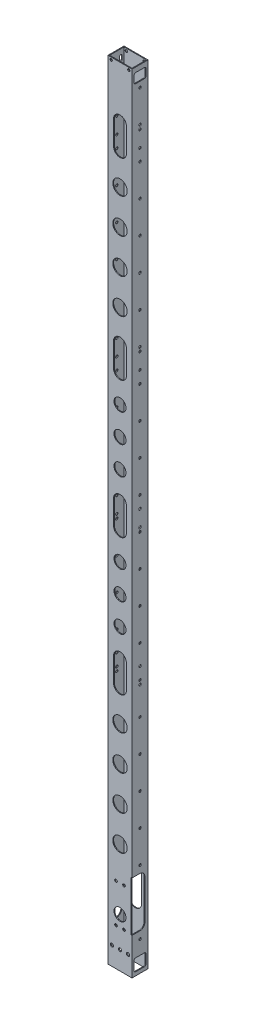
SolidWorks part; units mm, degrees
material "6061 合金"
ref_plane "Front" through (0, 0, 0) normal (0, 0, 1) x (1, 0, 0)
ref_plane "Top" through (0, 0, 0) normal (0, 1, 0) x (1, 0, 0)
ref_plane "Right" through (0, 0, 0) normal (1, 0, 0) x (0, 0, -1)
sketch "草图1" plane through (0, 0, 0) normal (0, 1, 0) x (1, 0, 0)
  line L1 (-15, -10) -> (15, -10)
  line L2 (-15, -10) -> (-15, 10)
  line L3 (-15, 10) -> (15, 10)
  line L4 (15, -10) -> (15, 10)
  line L5 (-15, -10) -> (15, 10) construction
  line L6 (-15, 10) -> (15, -10) construction
  line L7 (-14, -9) -> (14, -9)
  line L8 (-14, -9) -> (-14, 9)
  line L9 (-14, 9) -> (14, 9)
  line L10 (14, -9) -> (14, 9)
  line L11 (-14, -9) -> (14, 9) construction
  line L12 (-14, 9) -> (14, -9) construction
  point P0 (0, 0)
  point P5 (0, 0)
  dimension "D1" = 20
  dimension "D2" = 30
  dimension "D3" = 1
  dimension "D4" = 1
extrude "凸台-拉伸1" add sketch "草图1" along normal blind 980
sketch "草图3" plane through (15, 0, 0) normal (1, 0, 0) x (0, 0, -1)
  line L0 (0, 310) -> (0, 330) construction
  line L1 (0, 0) -> (0, 50000) construction
  line L2 (0, 910) -> (0, 890) construction
  line L4 (-10, 980) -> (10, 980) construction
  line L5 (-10, 490) -> (10, 490) construction
  line L6 (-10, 980) -> (-10, 0) construction
  line L7 (10, 980) -> (10, 0) construction
  line L8 (0, 500) -> (0, 480) construction
  line L9 (0, 670) -> (0, 650) construction
  line L10 (0, 70) -> (0, 90) construction
  circle A4 centre (0, 890) radius 1.5
  circle A5 centre (0, 910) radius 1.5
  circle A10 centre (0, 500) radius 1.5
  circle A11 centre (0, 480) radius 1.5
  circle A12 centre (0, 670) radius 1.5
  circle A13 centre (0, 650) radius 1.5
  circle A14 centre (0, 330) radius 1.5
  circle A15 centre (0, 310) radius 1.5
  circle A16 centre (0, 70) radius 1.5
  circle A17 centre (0, 90) radius 1.5
  dimension "D6" = 3
  dimension "D8" = 3
  dimension "D9" = 3
  dimension "D12" = 70
  dimension "D15" = 20
  dimension "D16" = 3
  dimension "D7" = 3
  dimension "D11" = 10
  dimension "D14" = 3
  dimension "D10" = 20
  dimension "D13" = 20
  dimension "D17" = 220
extrude "切除-拉伸2" cut sketch "草图3" against normal through all
sketch "草图4" plane through (15, 0, 0) normal (1, 0, 0) x (0, 0, -1)
  line L0 (0, 0) -> (0, 50000) construction
  line L1 (-10, 0) -> (10, 0) construction
  line L2 (-10, 980) -> (10, 980) construction
  line L3 (5, 968) -> (5, 972) construction
  line L4 (3.4, 968) -> (3.4, 972)
  line L5 (6.6, 968) -> (6.6, 972)
  line L6 (-5, 968) -> (-5, 972) construction
  line L7 (-3.4, 968) -> (-3.4, 972)
  line L8 (-6.6, 968) -> (-6.6, 972)
  circle A0 centre (-5, 10) radius 1.6 construction
  circle A1 centre (5, 10) radius 1.6 construction
  circle A2 centre (-5, 970) radius 1.6 construction
  circle A3 centre (5, 970) radius 1.6 construction
  arc A4 (3.4, 968) -> (6.6, 968) centre (5, 968) ccw
  arc A5 (6.6, 972) -> (3.4, 972) centre (5, 972) ccw
  arc A6 (-3.4, 968) -> (-6.6, 968) centre (-5, 968) cw
  arc A7 (-6.6, 972) -> (-3.4, 972) centre (-5, 972) cw
  point P17 (5, 970)
  point P24 (-5, 970)
  dimension "D1" = 3.2
  dimension "D4" = 3.2
  dimension "D7" = 1.6
  dimension "D2" = 10
  dimension "D3" = 10
  dimension "D5" = 10
  dimension "D6" = 10
  dimension "D8" = 4
extrude "切除-拉伸3" cut sketch "草图4" against normal through all
sketch "草图5" plane through (15, 0, 0) normal (1, 0, 0) x (0, 0, -1)
  line L0 (0, 0) -> (0, 50000) construction
  line L1 (10, 968) -> (-10, 968) construction
  line L2 (10, 980) -> (10, 0) construction
  line L3 (-10, 980) -> (-10, 0) construction
  line L4 (-10, 980) -> (10, 980) construction
  line L6 (-7.5, 974) -> (7.5, 974)
  line L7 (-7.5, 974) -> (-7.5, 962)
  line L8 (-7.5, 962) -> (7.5, 962)
  line L9 (7.5, 974) -> (7.5, 962)
  line L10 (-7.5, 974) -> (7.5, 962) construction
  line L11 (-7.5, 962) -> (7.5, 974) construction
  point P13 (0, 968)
  dimension "D1" = 12
  dimension "D2" = 12
  dimension "D3" = 15
extrude "切除-拉伸4" cut sketch "草图5" against normal blind 10
sketch "草图6" plane through (0, 0, -10) normal (0, 0, -1) x (-1, 0, 0)
  line L0 (-15, 91.5) -> (-15, 88.5) construction
  line L1 (-15, 71.5) -> (-15, 68.5) construction
  line L2 (-15, 91.5) -> (-15, 88.5) construction
  line L3 (-15, 71.5) -> (-15, 68.5) construction
  line L4 (-15, 891.5) -> (-15, 888.5) construction
  line L5 (-15, 911.5) -> (-15, 908.5) construction
  line L6 (-15, 671.5) -> (-15, 668.5) construction
  line L7 (-15, 651.5) -> (-15, 648.5) construction
  line L8 (-15, 501.5) -> (-15, 498.5) construction
  line L9 (-15, 481.5) -> (-15, 478.5) construction
  line L10 (-15, 331.5) -> (-15, 328.5) construction
  line L11 (-15, 311.5) -> (-15, 308.5) construction
  line L12 (-15, 891.5) -> (-15, 888.5) construction
  line L13 (-15, 911.5) -> (-15, 908.5) construction
  line L14 (-15, 671.5) -> (-15, 668.5) construction
  line L15 (-15, 651.5) -> (-15, 648.5) construction
  line L16 (-15, 501.5) -> (-15, 498.5) construction
  line L17 (-15, 481.5) -> (-15, 478.5) construction
  line L18 (-15, 331.5) -> (-15, 328.5) construction
  line L19 (-15, 311.5) -> (-15, 308.5) construction
  line L20 (0, 65) -> (0, 95) construction
  line L21 (-8, 65) -> (-8, 95)
  line L22 (8, 65) -> (8, 95)
  line L23 (0, 475) -> (0, 505) construction
  line L24 (-15, 88.5) -> (-15, 71.5) construction
  line L25 (-15, 80) -> (-40.807, 80) construction
  line L26 (0, 305) -> (0, 335) construction
  line L27 (-8, 305) -> (-8, 335)
  line L28 (8, 305) -> (8, 335)
  line L29 (0, 65) -> (0, 305) construction
  line L30 (-8, 475) -> (-8, 505)
  line L31 (8, 475) -> (8, 505)
  line L32 (0, 645) -> (0, 675) construction
  line L33 (-8, 645) -> (-8, 675)
  line L34 (8, 645) -> (8, 675)
  line L35 (0, 305) -> (0, 475) construction
  line L36 (0, 885) -> (0, 915) construction
  line L37 (-8, 885) -> (-8, 915)
  line L38 (8, 885) -> (8, 915)
  line L39 (0, 645) -> (0, 885) construction
  line L40 (0, 490) -> (-90.401, 490) construction
  arc A0 (-8, 65) -> (8, 65) centre (0, 65) ccw
  arc A1 (8, 95) -> (-8, 95) centre (0, 95) ccw
  arc A2 (-8, 305) -> (8, 305) centre (0, 305) ccw
  arc A3 (8, 335) -> (-8, 335) centre (0, 335) ccw
  arc A4 (-8, 475) -> (8, 475) centre (0, 475) ccw
  arc A5 (8, 505) -> (-8, 505) centre (0, 505) ccw
  arc A6 (-8, 645) -> (8, 645) centre (0, 645) ccw
  arc A7 (8, 675) -> (-8, 675) centre (0, 675) ccw
  arc A8 (-8, 885) -> (8, 885) centre (0, 885) ccw
  arc A9 (8, 915) -> (-8, 915) centre (0, 915) ccw
  circle A10 centre (0, 135) radius 9
  circle A11 centre (0, 178.3333) radius 9
  circle A12 centre (0, 221.6667) radius 9
  circle A13 centre (0, 265) radius 9
  circle A14 centre (0, 845) radius 9
  circle A16 centre (0, 801.6667) radius 9
  circle A17 centre (0, 758.3333) radius 9
  circle A18 centre (0, 715) radius 9
  circle A19 centre (0, 440) radius 7.5
  circle A20 centre (0, 405) radius 7.5
  circle A21 centre (0, 370) radius 7.5
  circle A22 centre (0, 610) radius 7.5
  circle A23 centre (0, 575) radius 7.5
  circle A24 centre (0, 540) radius 7.5
  point P23 (0, 80)
  point P34 (0, 320)
  point P42 (0, 490)
  point P49 (0, 660)
  point P58 (0, 900)
  dimension "D1" = 8
  dimension "D10" = 18
  dimension "D11" = 40
  dimension "D12" = 40
  dimension "D13" = 43.3333
  dimension "D14" = 40
  dimension "D16" = 40
  dimension "D18" = 35
  dimension "D19" = 35
  dimension "D20" = 35
  dimension "D21" = 15
  dimension "D2" = 30
  dimension "D3" = 2
  dimension "D4" = 240
  dimension "D5" = 3
  dimension "D6" = 170
  dimension "D8" = 240
  dimension "D9" = 4
  dimension "D7" = 2
  dimension "D15" = 4
  dimension "D17" = 3
extrude "切除-拉伸5" cut sketch "草图6" against normal through all
sketch "草图7" plane through (15, 0, 0) normal (1, 0, 0) x (0, 0, -1)
  line L1 (-10, 980) -> (-10, 0) construction
  line L2 (-10, 0) -> (10, 0) construction
  line L3 (0, 0) -> (0, 24.669) construction
  line L4 (-10, 980) -> (10, 980) construction
  circle A0 centre (-5, 5) radius 1.5
  circle A1 centre (5, 5) radius 1.5
  circle A2 centre (-5, 975) radius 1.5
  circle A3 centre (5, 975) radius 1.5
  dimension "D1" = 5
  dimension "D2" = 5
  dimension "D3" = 3
  dimension "D4" = 5
  dimension "D5" = 5
  dimension "D6" = 3
extrude "切除-拉伸6" [suppressed] cut sketch "草图7" against normal through all
sketch "草图9" plane through (0, 0, 10) normal (0, 0, 1) x (1, 0, 0)
  line L0 (15, 980) -> (15, 0) construction
  line L1 (-15, 0) -> (15, 0) construction
  line L2 (0, 0) -> (0, 1062.0992) construction
  line L3 (-15, 980) -> (15, 980) construction
  circle A0 centre (11, 3) radius 1.5 construction
  circle A1 centre (11, 977) radius 1.5
  circle A2 centre (-11, 3) radius 1.5 construction
  circle A3 centre (-11, 977) radius 1.5
  dimension "D3" = 3
  dimension "D4" = 4
  dimension "D5" = 3
  dimension "D1" = 4
  dimension "D2" = 3
extrude "切除-拉伸7" cut sketch "草图9" against normal through all
sketch "草图13" plane through (0, 0, 0) normal (0, -1, 0) x (1, 0, 0)
  line L4 (15, -10) -> (15, 10)
  line L5 (15, 10) -> (-15, 10)
  line L6 (-15, 10) -> (-15, -10)
  line L7 (-15, -10) -> (15, -10)
  line L8 (15, -10) -> (15, 10)
  line L9 (15, 10) -> (-15, 10)
  line L10 (-15, 10) -> (-15, -10)
  line L11 (-15, -10) -> (15, -10)
  line L12 (14, 9) -> (-14, 9)
  line L13 (14, -9) -> (14, 9)
  line L14 (-14, -9) -> (14, -9)
  line L15 (-14, 9) -> (-14, -9)
  line L16 (14, 9) -> (-14, 9)
  line L17 (14, -9) -> (14, 9)
  line L18 (-14, -9) -> (14, -9)
  line L19 (-14, 9) -> (-14, -9)
  dimension "D1" = 0
  dimension "D2" = 0
extrude "凸台-拉伸2" add sketch "草图13" along normal blind 10
sketch "草图11" plane through (-14, 0, 0) normal (1, 0, 0) x (0, 0, -1)
  line L0 (0, 0) -> (0, 111.3677) construction
  line L1 (-5, 5) -> (-5, 15) construction
  line L2 (-6.6, 5) -> (-6.6, 15)
  line L3 (-3.4, 5) -> (-3.4, 15)
  line L4 (5, 5) -> (5, 15) construction
  line L5 (6.6, 5) -> (6.6, 15)
  line L6 (3.4, 5) -> (3.4, 15)
  line L8 (10, -10) -> (-10, -10) construction
  arc A0 (-6.6, 5) -> (-3.4, 5) centre (-5, 5) ccw
  arc A1 (-3.4, 15) -> (-6.6, 15) centre (-5, 15) ccw
  arc A2 (6.6, 5) -> (3.4, 5) centre (5, 5) cw
  arc A3 (3.4, 15) -> (6.6, 15) centre (5, 15) cw
  point P5 (-5, 10)
  point P12 (5, 10)
  dimension "D4" = 1.6
  dimension "D1" = 10
  dimension "D2" = 20
  dimension "D3" = 10
extrude "切除-拉伸8" cut sketch "草图11" against normal blind 60
sketch "草图15" plane through (15, 0, 0) normal (1, 0, 0) x (0, 0, -1)
  line L0 (0, -10) -> (0, 26.437) construction
  line L1 (10, -10) -> (-10, -10) construction
  line L3 (-7.5, 17.5) -> (7.5, 17.5)
  line L4 (-7.5, 17.5) -> (-7.5, 2.5)
  line L5 (-7.5, 2.5) -> (7.5, 2.5)
  line L6 (7.5, 17.5) -> (7.5, 2.5)
  line L7 (-7.5, 17.5) -> (7.5, 2.5) construction
  line L8 (-7.5, 2.5) -> (7.5, 17.5) construction
  point P5 (0, 10)
  dimension "D1" = 20
  dimension "D2" = 15
  dimension "D3" = 15
extrude "切除-拉伸10" cut sketch "草图15" against normal blind 5
fillet "圆角1" radius 2 4 edges at (14.5, 2.5, -7.5) (14.5, 2.5, 7.5) (14.5, 17.5, -7.5) (14.5, 17.5, 7.5)
sketch "草图16" plane through (0, 0, 10) normal (0, 0, 1) x (1, 0, 0)
  line L0 (0, -10) -> (0, 90.7842) construction
  line L1 (15, -10) -> (-15, -10) construction
  circle A0 centre (10, 21) radius 2
  circle A1 centre (0, 21) radius 2
  circle A2 centre (-10, 21) radius 2
  dimension "D1" = 31
  dimension "D2" = 4
  dimension "D3" = 20
extrude "切除-拉伸11" cut sketch "草图16" against normal blind 90
fillet "圆角2" radius 2 4 edges at (14.5, 962, -7.5) (14.5, 962, 7.5) (14.5, 974, 7.5) (14.5, 974, -7.5)
sketch "草图17" plane through (15, 0, 0) normal (1, 0, 0) x (0, 0, -1)
  line L0 (-10, 980) -> (10, 980) construction
  circle A0 centre (0, 955) radius 1.5
  circle A1 centre (0, 915) radius 1.5
  circle A2 centre (0, 875) radius 1.5
  circle A3 centre (0, 835) radius 1.5
  circle A4 centre (0, 795) radius 1.5
  circle A5 centre (0, 755) radius 1.5
  circle A6 centre (0, 715) radius 1.5
  circle A7 centre (0, 675) radius 1.5
  circle A8 centre (0, 635) radius 1.5
  circle A9 centre (0, 595) radius 1.5
  circle A10 centre (0, 555) radius 1.5
  circle A11 centre (0, 515) radius 1.5
  circle A12 centre (0, 475) radius 1.5
  circle A13 centre (0, 435) radius 1.5
  circle A14 centre (0, 395) radius 1.5
  circle A15 centre (0, 355) radius 1.5
  circle A16 centre (0, 315) radius 1.5
  circle A17 centre (0, 275) radius 1.5
  circle A18 centre (0, 235) radius 1.5
  circle A19 centre (0, 195) radius 1.5
  circle A20 centre (0, 155) radius 1.5
  circle A21 centre (0, 115) radius 1.5
  circle A22 centre (0, 75) radius 1.5
  circle A23 centre (0, 35) radius 1.5
  dimension "D1" = 3
  dimension "D3" = 25
  dimension "D2" = 24
extrude "切除-拉伸12" cut sketch "草图17" against normal blind 40
sketch "草图20" plane through (15, 0, 0) normal (1, 0, 0) x (0, 0, -1)
  line L0 (0, 0) -> (0, 121.9481) construction
  line L1 (0, 50) -> (0, 100) construction
  line L2 (-6, 50) -> (-6, 100)
  line L3 (6, 50) -> (6, 100)
  line L4 (10, -10) -> (-10, -10) construction
  arc A0 (-6, 50) -> (6, 50) centre (0, 50) ccw
  arc A1 (6, 100) -> (-6, 100) centre (0, 100) ccw
  point P5 (0, 75)
  dimension "D2" = 6
  dimension "D3" = 60
  dimension "D1" = 50
extrude "切除-拉伸15" cut sketch "草图20" against normal blind 51
sketch "草图21" plane through (0, 0, 10) normal (0, 0, 1) x (1, 0, 0)
  line L1 (-11.7833, 108.871) -> (10.404, 108.871)
  line L2 (-11.7833, 108.871) -> (-11.7833, 43.5326)
  line L3 (-11.7833, 43.5326) -> (10.404, 43.5326)
  line L4 (10.404, 108.871) -> (10.404, 43.5326)
extrude "凸台-拉伸3" add sketch "草图21" against normal blind 1
sketch "草图22" plane through (0, 0, 10) normal (0, 0, 1) x (1, 0, 0)
  line L0 (0, 92.5342) -> (0, -20.6994) construction
  line L1 (15, -10) -> (-15, -10) construction
  circle A0 centre (5, 45) radius 1.65
  circle A1 centre (-5, 45) radius 1.65
  circle A2 centre (5, 93) radius 1.65
  circle A3 centre (-5, 93) radius 1.65
  dimension "D1" = 3.3
  dimension "D4" = 10
  dimension "D5" = 48
  dimension "D6" = 5
  dimension "D7" = 55
  dimension "D2" = 2
  dimension "D3" = 2
extrude "切除-拉伸16" cut sketch "草图22" against normal blind 1
sketch "草图23" plane through (0, 0, 10) normal (0, 0, 1) x (1, 0, 0)
  circle A0 centre (0, 59.25) radius 7.5
  circle A1 centre (5, 45) radius 1.65 construction
  dimension "D1" = 15
  dimension "D2" = 14.25
extrude "切除-拉伸17" cut sketch "草图23" against normal blind 10
sketch "草图24" plane through (0, -10, 0) normal (0, -1, 0) x (1, 0, 0)
  line L1 (-15, 10) -> (15, 10)
  line L2 (-15, 10) -> (-15, -10)
  line L3 (-15, -10) -> (15, -10)
  line L4 (15, 10) -> (15, -10)
extrude "切除-拉伸18" cut sketch "草图24" against normal blind 8
sketch "草图25" plane through (15, 0, 0) normal (1, 0, 0) x (0, 0, -1)
  line L1 (0, 44) -> (-36.2729, 44)
  line L2 (0, 44) -> (0, 106)
  line L3 (0, 106) -> (-36.2729, 106)
  line L4 (-36.2729, 44) -> (-36.2729, 106)
  arc A0 (-6, 50) -> (6, 50) centre (0, 50) ccw construction
  arc A1 (6, 100) -> (-6, 100) centre (0, 100) ccw construction
extrude "切除-拉伸19" cut sketch "草图25" against normal blind 1
